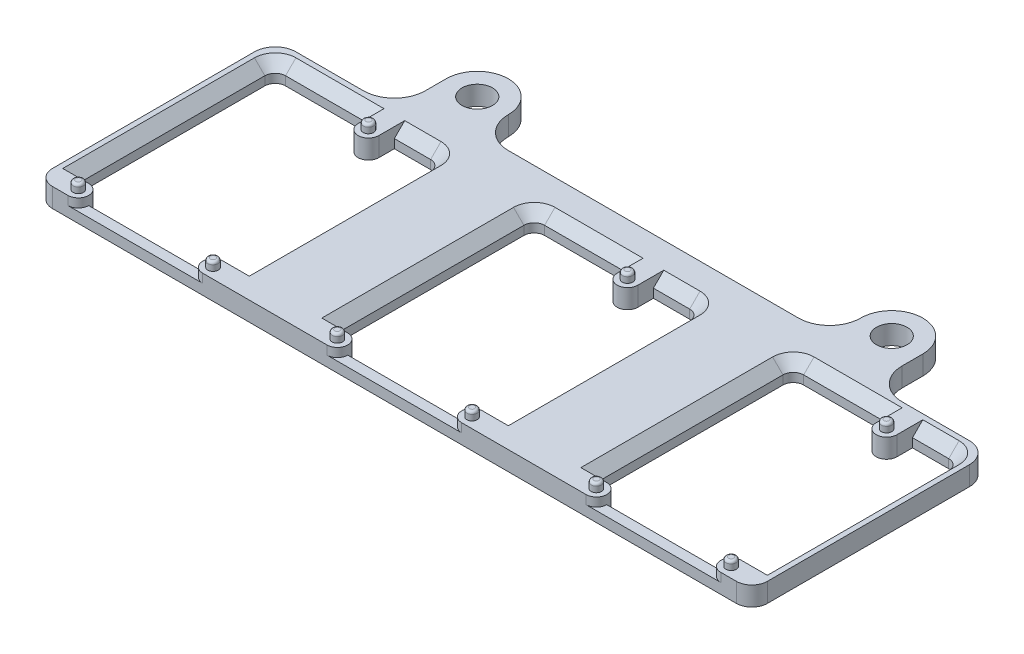
SolidWorks part; units mm, degrees
ref_plane "Front Plane" through (0, 0, 0) normal (0, 0, 1) x (1, 0, 0)
ref_plane "Top Plane" through (0, 0, 0) normal (0, 1, 0) x (1, 0, 0)
ref_plane "Right Plane" through (0, 0, 0) normal (1, 0, 0) x (0, 0, -1)
sketch "Sketch1" plane through (0, 0, 0) normal (0, 1, 0) x (1, 0, 0)
  line L1 (-69, 23) -> (69, 23)
  line L2 (-69, 23) -> (-69, -23)
  line L3 (-69, -23) -> (69, -23)
  line L4 (69, 23) -> (69, -23)
  line L5 (-69, 23) -> (69, -23) construction
  line L6 (-69, -23) -> (69, 23) construction
  point P0 (0, 0)
  dimension "D1" = 138
  dimension "D2" = 46
extrude "Boss-Extrude1" add sketch "Sketch1" along normal blind 3.7 contours L1 L4 L3 L2
sketch "Sketch2" plane through (0, 0, 0) normal (0, 1, 0) x (1, 0, 0)
  line L0 (-69, 23) -> (69, 23) construction
  line L1 (34, 23) -> (46, 23)
  line L2 (34, 23) -> (34, 39)
  line L3 (34, 39) -> (46, 39)
  line L4 (46, 23) -> (46, 39)
  line L5 (40, 39) -> (40, 23) construction
  line L7 (34, 23) -> (0, 23)
  line L8 (34, 23) -> (34, 27)
  line L9 (34, 27) -> (0, 27)
  line L10 (0, 23) -> (0, 27)
  circle A0 centre (40, 33) radius 2.95
  dimension "D5" = 5.9
  dimension "D1" = 40
  dimension "D2" = 12
  dimension "D3" = 16
  dimension "D4" = 10
  dimension "D6" = 4
extrude "Boss-Extrude2" add sketch "Sketch2" along direction (0, 1, 0) on the side of the normal up to surface (3.7 mm away) contours L10 L7 L2 L9 | L5 L3 L2 L1 A0 | L3 L5 A0 L1 L4 up to face at (0, 3.7, 0)
fillet "Fillet1" radius 6 4 edges at (34, 1.85, -39) (46, 1.85, -39) (46, 1.85, -23) (34, 1.85, -27)
mirror "Mirror1" about plane through (0, 0, 0) normal (1, 0, 0) of "Fillet1", "Boss-Extrude2"
sketch "Sketch3" plane through (0, 3.7, 0) normal (0, 1, 0) x (1, 0, 0)
  line L0 (0, 26.7252) -> (0, -23) construction
  line L1 (-69, -23) -> (69, -23) construction
  line L3 (-16, 20) -> (16, 20)
  line L4 (-16, 20) -> (-16, -23)
  line L5 (-16, -23) -> (16, -23)
  line L6 (16, 20) -> (16, -23)
  line L7 (-16, 20) -> (16, -23) construction
  line L8 (-16, -23) -> (16, 20) construction
  line L9 (-69, -21) -> (69, -21) construction
  line L10 (-69, 23) -> (-69, -23) construction
  line L11 (69, 23) -> (69, -23) construction
  line L12 (-13, -23) -> (-16, -23)
  line L13 (-13, -19) -> (-16, -19)
  line L14 (-69, 23) -> (-52, 23) construction
  line L15 (16, -19) -> (13, -19)
  line L16 (3, 17) -> (3, 20)
  line L17 (7, 17) -> (7, 20)
  circle A0 centre (-13, -21) radius 2
  circle A1 centre (13, -21) radius 2
  circle A2 centre (5, 17) radius 2
  point P4 (0, -1.5)
  dimension "D6" = 4
  dimension "D7" = 4
  dimension "D8" = 4
  dimension "D1" = 32
  dimension "D2" = 3
  dimension "D3" = 44
  dimension "D4" = 13
  dimension "D5" = 13
  dimension "D9" = 6
  dimension "D10" = 5
extrude "Cut-Extrude1" cut sketch "Sketch3" against normal through all
fillet "Fillet2" radius 2 2 edges at (16, 1.85, -20) (-16, 1.85, -20)
sketch "Sketch4" plane through (0, 3.7, 0) normal (0, 1, 0) x (1, 0, 0)
  circle A0 centre (5, 17) radius 1
  circle A1 centre (13, -21) radius 1
  circle A2 centre (-13, -21) radius 1
  dimension "D1" = 2
  dimension "D2" = 2
  dimension "D3" = 2
extrude "Boss-Extrude3" add sketch "Sketch4" along normal blind 1.6
fillet "Fillet3" radius 0.5 3 edges at (-13, 5.3, 22) (13, 5.3, 22) (5, 5.3, -16)
sketch "Sketch5" plane through (0, 0, 0) normal (0, 1, 0) x (1, 0, 0)
  line L1 (-13, -23) -> (13, -23)
  line L2 (-13, -23) -> (-13, -21)
  line L3 (-13, -21) -> (13, -21)
  line L4 (13, -23) -> (13, -21)
extrude "Boss-Extrude4" add sketch "Sketch5" along normal blind 2
pattern_linear "LPattern1" count 2 spacing 50 along (1, 0, 0) count 2 spacing 50 along (-1, 0, 0) of "Cut-Extrude1", "Fillet2", "Boss-Extrude3", "Fillet3", "Boss-Extrude4" pattern seed only yes
fillet "Fillet4" radius 4 2 edges at (69, 1.85, -23) (-69, 1.85, -23)
fillet "Fillet5" radius 3 2 edges at (-69, 1.85, 23) (69, 1.85, 23)
chamfer "Chamfer1" distance 2 angle 45 18 edges at (60.5, 3.7, -20) (65.4142, 3.7, -19.4142) (66, 3.7, 0.5) (44.5, 3.7, -20) (34.5858, 3.7, -19.4142) (34, 3.7, 0.5) (10.5, 3.7, -20) (15.4142, 3.7, -19.4142) (16, 3.7, 0.5) (-5.5, 3.7, -20) (-15.4142, 3.7, -19.4142) (-16, 3.7, 0.5) (-34, 3.7, 0.5) (-34.5858, 3.7, -19.4142) (-39.5, 3.7, -20) (-55.5, 3.7, -20) (-65.4142, 3.7, -19.4142) (-66, 3.7, 0.5)
